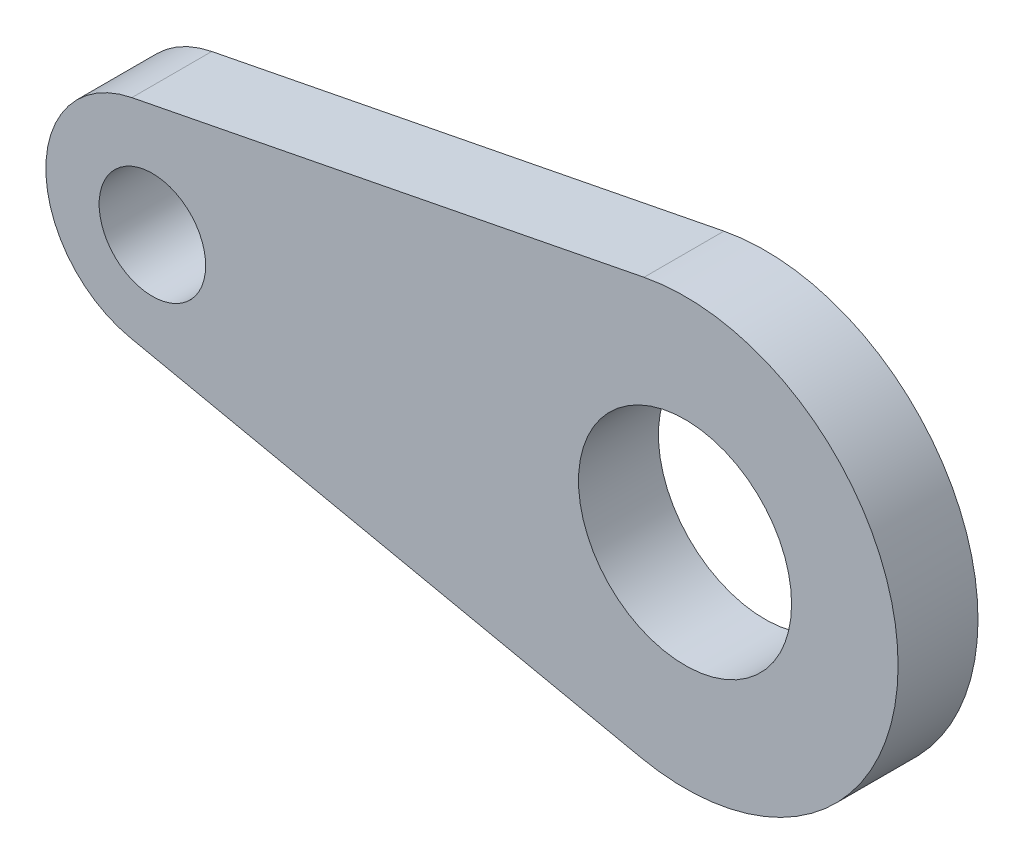
SolidWorks part; units mm, degrees
ref_plane "Plano frontal" through (0, 0, 0) normal (0, 0, 1) x (1, 0, 0)
ref_plane "Plano superior" through (0, 0, 0) normal (0, 1, 0) x (1, 0, 0)
ref_plane "Plano direito" through (0, 0, 0) normal (1, 0, 0) x (0, 0, -1)
sketch "Esboço1" plane through (0, 0, 0) normal (0, 0, 1) x (1, 0, 0)
  line L0 (-4.1492, -18.8024) -> (91.7016, -39.1297)
  line L3 (-3.9944, 20.3601) -> (92.2993, 39.2517)
  arc A0 (-3.8503, 20.3884) -> (-4.1492, -18.8024) centre (0, 0.7625) ccw
  arc A2 (91.7016, -39.1297) -> (92.2993, 39.2517) centre (100, 0) ccw
  circle A3 centre (0, 0) radius 10
  circle A4 centre (100, 0) radius 20
  dimension "D2" = 40
  dimension "D3" = 80
  dimension "D4" = 20
  dimension "D5" = 40
  dimension "D1" = 100
extrude "Ressalto-extrusão3" add sketch "Esboço1" along normal blind 15 contours L0 A2 L3 A0 A4 A3 region at (65.369, 0.2952, 0)
